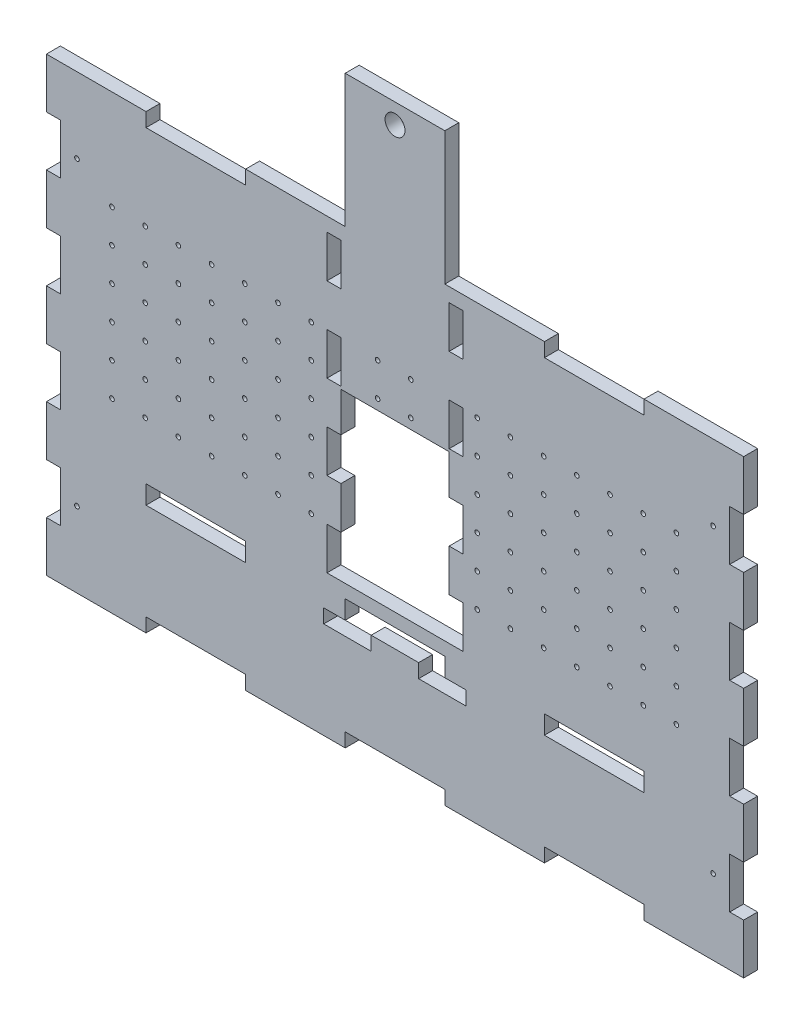
SolidWorks part; units mm, degrees
ref_plane "Front Plane" through (0, 0, 0) normal (0, 0, 1) x (1, 0, 0)
ref_plane "Top Plane" through (0, 0, 0) normal (0, 1, 0) x (1, 0, 0)
ref_plane "Right Plane" through (0, 0, 0) normal (1, 0, 0) x (0, 0, -1)
sketch "Sketch1" plane through (0, 0, 0) normal (0, 0, 1) x (1, 0, 0)
  line L1 (-127.8759, 88.4641) -> (138.8241, 88.4641)
  line L2 (-127.8759, 88.4641) -> (-127.8759, -84.2559)
  line L3 (-127.8759, -84.2559) -> (138.8241, -84.2559)
  line L4 (138.8241, 88.4641) -> (138.8241, -84.2559)
  dimension "D1" = 266.7
  dimension "D2" = 172.72
extrude "Boss-Extrude1" add sketch "Sketch1" along normal blind 5.334
sketch "Sketch2" plane through (0, 0, 5.334) normal (0, 0, 1) x (1, 0, 0)
  line L0 (-127.8759, -84.2559) -> (138.8241, -84.2559) construction
  line L1 (-89.7759, -84.2559) -> (-51.6759, -84.2559)
  line L2 (-89.7759, -84.2559) -> (-89.7759, -78.9219)
  line L3 (-89.7759, -78.9219) -> (-51.6759, -78.9219)
  line L4 (-51.6759, -84.2559) -> (-51.6759, -78.9219)
  line L5 (-89.7759, -78.9219) -> (-127.8759, -78.9219) construction
  line L6 (-13.5759, -84.2559) -> (24.5241, -84.2559)
  line L7 (-13.5759, -84.2559) -> (-13.5759, -78.9219)
  line L8 (-13.5759, -78.9219) -> (24.5241, -78.9219)
  line L9 (24.5241, -84.2559) -> (24.5241, -78.9219)
  line L10 (62.6241, -84.2559) -> (100.7241, -84.2559)
  line L11 (62.6241, -84.2559) -> (62.6241, -78.9219)
  line L12 (62.6241, -78.9219) -> (100.7241, -78.9219)
  line L13 (100.7241, -84.2559) -> (100.7241, -78.9219)
  line L14 (-127.8759, 88.4641) -> (-127.8759, -84.2559) construction
  line L15 (-51.6759, -78.9219) -> (-13.5759, -78.9219) construction
  line L16 (24.5241, -78.9219) -> (62.6241, -78.9219) construction
  line L17 (62.6241, -78.9219) -> (62.364, -79.7896) construction
  line L18 (100.7241, -78.9219) -> (138.8241, -78.9219) construction
  line L19 (138.8241, -84.2559) -> (138.8241, 88.4641) construction
  line L20 (-127.8759, 2.1041) -> (138.8241, 2.1041) construction
  line L21 (100.7241, 88.4641) -> (100.7241, 83.1301)
  line L22 (62.6241, 83.1301) -> (100.7241, 83.1301)
  line L23 (62.6241, 88.4641) -> (62.6241, 83.1301)
  line L24 (24.5241, 88.4641) -> (24.5241, 83.1301)
  line L25 (-13.5759, 83.1301) -> (24.5241, 83.1301)
  line L26 (-13.5759, 88.4641) -> (-13.5759, 83.1301)
  line L27 (-51.6759, 88.4641) -> (-51.6759, 83.1301)
  line L28 (-89.7759, 83.1301) -> (-51.6759, 83.1301)
  line L29 (-89.7759, 88.4641) -> (-89.7759, 83.1301)
  line L30 (62.6241, 88.4641) -> (100.7241, 88.4641)
  line L31 (-13.5759, 88.4641) -> (24.5241, 88.4641)
  line L32 (-89.7759, 88.4641) -> (-51.6759, 88.4641)
  dimension "D1" = 5.334
extrude "Cut-Extrude1" cut sketch "Sketch2" against normal through all
sketch "Sketch5" plane through (0, 0, 5.334) normal (0, 0, 1) x (1, 0, 0)
  line L0 (-51.6759, -34.8224) -> (-13.5759, -34.8224) construction
  line L1 (-89.7759, -34.8224) -> (-51.6759, -34.8224)
  line L2 (-89.7759, -34.8224) -> (-89.7759, -41.9344)
  line L3 (-89.7759, -41.9344) -> (-51.6759, -41.9344)
  line L4 (-51.6759, -34.8224) -> (-51.6759, -41.9344)
  line L5 (-13.5759, -34.8224) -> (24.5241, -34.8224)
  line L6 (-13.5759, -34.8224) -> (-13.5759, -41.9344)
  line L7 (-13.5759, -41.9344) -> (24.5241, -41.9344)
  line L8 (24.5241, -34.8224) -> (24.5241, -41.9344)
  line L9 (62.6241, -34.8224) -> (100.7241, -34.8224)
  line L10 (62.6241, -34.8224) -> (62.6241, -41.9344)
  line L11 (62.6241, -41.9344) -> (100.7241, -41.9344)
  line L12 (100.7241, -34.8224) -> (100.7241, -41.9344)
  line L13 (-51.6759, -41.9344) -> (-13.5759, -41.9344) construction
  line L14 (24.5241, -34.8224) -> (62.6241, -34.8224) construction
  line L15 (24.5241, -41.9344) -> (62.6241, -41.9344) construction
  line L16 (-89.7759, -34.8224) -> (-127.8759, -34.8224) construction
  line L17 (-127.8759, 88.4641) -> (-127.8759, -84.2559) construction
  line L18 (-89.7759, -41.9344) -> (-127.8759, -41.9344) construction
  line L19 (100.7241, -34.8224) -> (138.8241, -34.8224) construction
  line L20 (138.8241, -84.2559) -> (138.8241, 88.4641) construction
  line L21 (100.7241, -41.9344) -> (138.8241, -41.9344) construction
  dimension "D1" = 7.112
extrude "Cut-Extrude3" cut sketch "Sketch5" against normal through all
sketch "Sketch8" plane through (0, 0, 5.334) normal (0, 0, 1) x (1, 0, 0)
  line L0 (-13.5759, -41.9344) -> (24.5241, -41.9344) construction
  line L1 (-21.7977, -47.2684) -> (-3.6478, -47.2684)
  line L2 (-21.7977, -47.2684) -> (-21.7977, -41.9344)
  line L3 (-21.7977, -41.9344) -> (-3.6478, -41.9344)
  line L4 (-3.6478, -47.2684) -> (-3.6478, -41.9344)
  line L5 (-3.6478, -47.2684) -> (14.5022, -47.2684) construction
  line L6 (14.5022, -41.9344) -> (32.6521, -41.9344)
  line L7 (14.5022, -41.9344) -> (14.5022, -47.2684)
  line L8 (14.5022, -47.2684) -> (32.6521, -47.2684)
  line L9 (32.6521, -41.9344) -> (32.6521, -47.2684)
  line L10 (14.5022, -47.2684) -> (14.3218, -49.4005) construction
  line L11 (14.5022, -41.9344) -> (-3.6478, -41.9344) construction
  line L12 (62.6241, -34.8224) -> (62.6241, -41.9344) construction
  line L13 (-51.6759, -41.9344) -> (-51.6759, -34.8224) construction
  dimension "D1" = 5.334
  dimension "D2" = 29.972
  dimension "D3" = 29.8782
extrude "Cut-Extrude6" cut sketch "Sketch8" against normal through all
sketch "Sketch9" plane through (0, 0, 5.334) normal (0, 0, 1) x (1, 0, 0)
  line L0 (-127.8759, 88.4641) -> (-127.8759, -84.2559) construction
  line L1 (-127.8759, -65.0647) -> (-122.5419, -65.0647)
  line L2 (-127.8759, -65.0647) -> (-127.8759, -45.8736)
  line L3 (-127.8759, -45.8736) -> (-122.5419, -45.8736)
  line L4 (-122.5419, -65.0647) -> (-122.5419, -45.8736)
  line L5 (-122.5419, 69.273) -> (-122.5419, 88.4641) construction
  line L6 (-127.8759, -26.6825) -> (-122.5419, -26.6825)
  line L7 (-127.8759, -26.6825) -> (-127.8759, -7.4914)
  line L8 (-127.8759, -7.4914) -> (-122.5419, -7.4914)
  line L9 (-122.5419, -26.6825) -> (-122.5419, -7.4914)
  line L10 (-127.8759, 11.6997) -> (-122.5419, 11.6997)
  line L11 (-127.8759, 11.6997) -> (-127.8759, 30.8908)
  line L12 (-127.8759, 30.8908) -> (-122.5419, 30.8908)
  line L13 (-122.5419, 11.6997) -> (-122.5419, 30.8908)
  line L14 (-127.8759, 50.0819) -> (-122.5419, 50.0819)
  line L15 (-127.8759, 50.0819) -> (-127.8759, 69.273)
  line L16 (-127.8759, 69.273) -> (-122.5419, 69.273)
  line L17 (-122.5419, 50.0819) -> (-122.5419, 69.273)
  line L18 (-89.7759, 88.4641) -> (-127.8759, 88.4641) construction
  line L19 (-122.5419, 50.0819) -> (-122.5419, 30.8908) construction
  line L20 (-122.5419, 11.6997) -> (-122.5419, -7.4914) construction
  line L21 (-122.5419, -26.6825) -> (-122.5419, -45.8736) construction
  line L22 (-122.5419, -65.0647) -> (-122.5419, -84.2559) construction
  line L23 (-127.8759, -84.2559) -> (-89.7759, -84.2559) construction
  line L24 (5.4741, 83.1301) -> (5.4741, -78.9219) construction
  line L25 (-13.5759, 83.1301) -> (24.5241, 83.1301) construction
  line L26 (24.5241, -78.9219) -> (-13.5759, -78.9219) construction
  line L27 (133.4901, -65.0647) -> (133.4901, -84.2559) construction
  line L28 (133.4901, -26.6825) -> (133.4901, -45.8736) construction
  line L29 (133.4901, 11.6997) -> (133.4901, -7.4914) construction
  line L30 (133.4901, 50.0819) -> (133.4901, 30.8908) construction
  line L31 (133.4901, 69.273) -> (133.4901, 88.4641) construction
  line L32 (133.4901, 50.0819) -> (133.4901, 69.273)
  line L33 (138.8241, 69.273) -> (133.4901, 69.273)
  line L34 (138.8241, 50.0819) -> (138.8241, 69.273)
  line L35 (138.8241, 50.0819) -> (133.4901, 50.0819)
  line L36 (133.4901, 11.6997) -> (133.4901, 30.8908)
  line L37 (138.8241, 30.8908) -> (133.4901, 30.8908)
  line L38 (138.8241, 11.6997) -> (138.8241, 30.8908)
  line L39 (138.8241, 11.6997) -> (133.4901, 11.6997)
  line L40 (133.4901, -26.6825) -> (133.4901, -7.4914)
  line L41 (138.8241, -7.4914) -> (133.4901, -7.4914)
  line L42 (138.8241, -26.6825) -> (138.8241, -7.4914)
  line L43 (138.8241, -26.6825) -> (133.4901, -26.6825)
  line L44 (133.4901, -65.0647) -> (133.4901, -45.8736)
  line L45 (138.8241, -45.8736) -> (133.4901, -45.8736)
  line L46 (138.8241, -65.0647) -> (138.8241, -45.8736)
  line L47 (138.8241, -65.0647) -> (133.4901, -65.0647)
  dimension "D1" = 5.334
extrude "Cut-Extrude7" cut sketch "Sketch9" against normal through all
sketch "Sketch10" plane through (0, 88.4641, 0) normal (0, 1, 0) x (1, 0, 0)
  line L1 (24.5241, -5.334) -> (62.6241, -5.334)
  line L2 (24.5241, -5.334) -> (24.5241, 0)
  line L3 (24.5241, 0) -> (62.6241, 0)
  line L4 (62.6241, -5.334) -> (62.6241, 0)
extrude "Boss-Extrude2" add sketch "Sketch10" along normal blind 50.8
sketch "Sketch11" plane through (0, 0, 0) normal (0, 0, -1) x (-1, 0, 0)
  line L0 (-24.5241, 83.1301) -> (-24.5241, 139.2641) construction
  line L1 (-24.5241, 88.4641) -> (-31.1281, 88.4641)
  line L2 (-24.5241, 88.4641) -> (-24.5241, 129.1041)
  line L3 (-24.5241, 129.1041) -> (-31.1281, 129.1041)
  line L4 (-31.1281, 88.4641) -> (-31.1281, 129.1041)
  line L5 (13.5759, 88.4641) -> (51.6759, 88.4641) construction
  dimension "D1" = 6.604
  dimension "D2" = 40.64
  dimension "D3" = 0
extrude "Cut-Extrude8" cut sketch "Sketch11" against normal through all
sketch "Sketch12" plane through (0, 0, 5.334) normal (0, 0, 1) x (1, 0, 0)
  line L0 (62.6241, 139.2641) -> (62.6241, 83.1301) construction
  circle A0 centre (43.5741, 130.4765) radius 3.81
  dimension "D1" = 19.05
extrude "Cut-Extrude9" cut sketch "Sketch12" against normal through all
sketch "Sketch14" plane through (0, 0, 5.334) normal (0, 0, 1) x (1, 0, 0)
  line L0 (-89.7759, 88.4641) -> (-127.8759, 88.4641) construction
  circle A0 centre (-102.7976, 50.3641) radius 0.889
  circle A1 centre (-90.0976, 50.3641) radius 0.889
  circle A2 centre (-77.3976, 50.3641) radius 0.889
  circle A3 centre (-64.6976, 50.3641) radius 0.889
  circle A4 centre (-51.9976, 50.3641) radius 0.889
  circle A5 centre (-39.2976, 50.3641) radius 0.889
  circle A6 centre (-26.5976, 50.3641) radius 0.889
  circle A8 centre (-1.1976, 50.3641) radius 0.889
  circle A9 centre (11.5024, 50.3641) radius 0.889
  circle A11 centre (36.9024, 50.3641) radius 0.889
  circle A12 centre (49.6024, 50.3641) radius 0.889
  circle A13 centre (62.3024, 50.3641) radius 0.889
  circle A14 centre (75.0024, 50.3641) radius 0.889
  circle A15 centre (87.7024, 50.3641) radius 0.889
  circle A16 centre (100.4024, 50.3641) radius 0.889
  circle A17 centre (113.1024, 50.3641) radius 0.889
  circle A18 centre (-102.7976, 37.6641) radius 0.889
  circle A19 centre (-90.0976, 37.6641) radius 0.889
  circle A20 centre (-77.3976, 37.6641) radius 0.889
  circle A21 centre (-64.6976, 37.6641) radius 0.889
  circle A22 centre (-51.9976, 37.6641) radius 0.889
  circle A23 centre (-39.2976, 37.6641) radius 0.889
  circle A24 centre (-26.5976, 37.6641) radius 0.889
  circle A26 centre (-1.1976, 37.6641) radius 0.889
  circle A27 centre (11.5024, 37.6641) radius 0.889
  circle A29 centre (36.9024, 37.6641) radius 0.889
  circle A30 centre (49.6024, 37.6641) radius 0.889
  circle A31 centre (62.3024, 37.6641) radius 0.889
  circle A32 centre (75.0024, 37.6641) radius 0.889
  circle A33 centre (87.7024, 37.6641) radius 0.889
  circle A34 centre (100.4024, 37.6641) radius 0.889
  circle A35 centre (113.1024, 37.6641) radius 0.889
  circle A36 centre (-102.7976, 24.9641) radius 0.889
  circle A37 centre (-90.0976, 24.9641) radius 0.889
  circle A38 centre (-77.3976, 24.9641) radius 0.889
  circle A39 centre (-64.6976, 24.9641) radius 0.889
  circle A40 centre (-51.9976, 24.9641) radius 0.889
  circle A41 centre (-39.2976, 24.9641) radius 0.889
  circle A42 centre (-26.5976, 24.9641) radius 0.889
  circle A44 centre (-1.1976, 24.9641) radius 0.889
  circle A45 centre (11.5024, 24.9641) radius 0.889
  circle A47 centre (36.9024, 24.9641) radius 0.889
  circle A48 centre (49.6024, 24.9641) radius 0.889
  circle A49 centre (62.3024, 24.9641) radius 0.889
  circle A50 centre (75.0024, 24.9641) radius 0.889
  circle A51 centre (87.7024, 24.9641) radius 0.889
  circle A52 centre (100.4024, 24.9641) radius 0.889
  circle A53 centre (113.1024, 24.9641) radius 0.889
  circle A54 centre (-102.7976, 12.2641) radius 0.889
  circle A55 centre (-90.0976, 12.2641) radius 0.889
  circle A56 centre (-77.3976, 12.2641) radius 0.889
  circle A57 centre (-64.6976, 12.2641) radius 0.889
  circle A58 centre (-51.9976, 12.2641) radius 0.889
  circle A59 centre (-39.2976, 12.2641) radius 0.889
  circle A60 centre (-26.5976, 12.2641) radius 0.889
  circle A65 centre (36.9024, 12.2641) radius 0.889
  circle A66 centre (49.6024, 12.2641) radius 0.889
  circle A67 centre (62.3024, 12.2641) radius 0.889
  circle A68 centre (75.0024, 12.2641) radius 0.889
  circle A69 centre (87.7024, 12.2641) radius 0.889
  circle A70 centre (100.4024, 12.2641) radius 0.889
  circle A71 centre (113.1024, 12.2641) radius 0.889
  circle A72 centre (-102.7976, -0.4359) radius 0.889
  circle A73 centre (-90.0976, -0.4359) radius 0.889
  circle A74 centre (-77.3976, -0.4359) radius 0.889
  circle A75 centre (-64.6976, -0.4359) radius 0.889
  circle A76 centre (-51.9976, -0.4359) radius 0.889
  circle A77 centre (-39.2976, -0.4359) radius 0.889
  circle A78 centre (-26.5976, -0.4359) radius 0.889
  circle A79 centre (-13.8976, -0.4359) radius 0.889
  circle A80 centre (-1.1976, -0.4359) radius 0.889
  circle A81 centre (11.5024, -0.4359) radius 0.889
  circle A82 centre (24.2024, -0.4359) radius 0.889
  circle A83 centre (36.9024, -0.4359) radius 0.889
  circle A84 centre (49.6024, -0.4359) radius 0.889
  circle A85 centre (62.3024, -0.4359) radius 0.889
  circle A86 centre (75.0024, -0.4359) radius 0.889
  circle A87 centre (87.7024, -0.4359) radius 0.889
  circle A88 centre (100.4024, -0.4359) radius 0.889
  circle A89 centre (113.1024, -0.4359) radius 0.889
  circle A90 centre (-102.7976, -13.1359) radius 0.889
  circle A91 centre (-90.0976, -13.1359) radius 0.889
  circle A92 centre (-77.3976, -13.1359) radius 0.889
  circle A93 centre (-64.6976, -13.1359) radius 0.889
  circle A94 centre (-51.9976, -13.1359) radius 0.889
  circle A95 centre (-39.2976, -13.1359) radius 0.889
  circle A96 centre (-26.5976, -13.1359) radius 0.889
  circle A97 centre (-13.8976, -13.1359) radius 0.889
  circle A98 centre (-1.1976, -13.1359) radius 0.889
  circle A99 centre (11.5024, -13.1359) radius 0.889
  circle A100 centre (24.2024, -13.1359) radius 0.889
  circle A101 centre (36.9024, -13.1359) radius 0.889
  circle A102 centre (49.6024, -13.1359) radius 0.889
  circle A103 centre (62.3024, -13.1359) radius 0.889
  circle A104 centre (75.0024, -13.1359) radius 0.889
  circle A105 centre (87.7024, -13.1359) radius 0.889
  circle A106 centre (100.4024, -13.1359) radius 0.889
  circle A107 centre (113.1024, -13.1359) radius 0.889
  circle A108 centre (-1.1976, 12.2641) radius 0.889 [skipped]
  circle A110 centre (11.5024, 12.2641) radius 0.889 [skipped]
  circle A116 centre (24.2024, 50.3641) radius 0.889 [skipped]
  circle A117 centre (-13.8976, 50.3641) radius 0.889 [skipped]
  dimension "D1" = 18
  dimension "D2" = 38.1
  dimension "D4" = 1.778
  dimension "D3" = 6
extrude "Cut-Extrude11" cut sketch "Sketch14" against normal through all
sketch "Sketch15" plane through (0, 0, 5.334) normal (0, 0, 1) x (1, 0, 0)
  line L1 (31.1281, 129.1041) -> (24.5241, 129.1041)
  line L2 (31.1281, 129.1041) -> (31.1281, 139.2641)
  line L3 (31.1281, 139.2641) -> (24.5241, 139.2641)
  line L4 (24.5241, 129.1041) -> (24.5241, 139.2641)
extrude "Cut-Extrude12" cut sketch "Sketch15" against normal through all
sketch "Sketch16" plane through (0, 0, 5.334) normal (0, 0, 1) x (1, 0, 0)
  line L0 (5.4741, 83.1301) -> (5.4741, -78.9219) construction
  line L1 (-15.2269, 33.7576) -> (26.1751, 33.7576)
  line L2 (-15.2269, 33.7576) -> (-15.2269, -29.7424)
  line L3 (-15.2269, -29.7424) -> (26.1751, -29.7424)
  line L4 (26.1751, 33.7576) -> (26.1751, -29.7424)
  line L5 (-13.5759, 83.1301) -> (24.5241, 83.1301) construction
  line L6 (24.5241, -78.9219) -> (-13.5759, -78.9219) construction
  line L7 (24.5241, -34.8224) -> (-13.5759, -34.8224) construction
  dimension "D1" = 63.5
  dimension "D2" = 41.402
  dimension "D3" = 20.701
  dimension "D4" = 5.08
extrude "Cut-Extrude13" cut sketch "Sketch16" against normal through all
sketch "Sketch17" plane through (0, 0, 5.334) normal (0, 0, 1) x (1, 0, 0)
  line L0 (-15.2269, 33.7576) -> (-15.2269, -29.7424) construction
  line L1 (-15.2269, -29.7424) -> (-20.5609, -29.7424)
  line L2 (-15.2269, -29.7424) -> (-15.2269, -13.6178)
  line L3 (-15.2269, -13.6178) -> (-20.5609, -13.6178)
  line L4 (-20.5609, -29.7424) -> (-20.5609, -13.6178)
  line L5 (-15.2269, 2.5069) -> (-20.5609, 2.5069)
  line L6 (-15.2269, 2.5069) -> (-15.2269, 18.6315)
  line L7 (-15.2269, 18.6315) -> (-20.5609, 18.6315)
  line L8 (-20.5609, 2.5069) -> (-20.5609, 18.6315)
  line L9 (-20.5609, -13.6178) -> (-20.5609, 2.5069) construction
  line L10 (-20.5609, 50.8808) -> (-15.2269, 50.8808)
  line L11 (-20.5609, 50.8808) -> (-20.5609, 34.7562)
  line L12 (-20.5609, 34.7562) -> (-15.2269, 34.7562)
  line L13 (-15.2269, 50.8808) -> (-15.2269, 34.7562)
  line L14 (-20.5609, 67.0055) -> (-15.2269, 67.0055)
  line L15 (-20.5609, 67.0055) -> (-20.5609, 83.1301)
  line L16 (-20.5609, 83.1301) -> (-15.2269, 83.1301)
  line L17 (-15.2269, 67.0055) -> (-15.2269, 83.1301)
  line L18 (-20.5609, 18.6315) -> (-20.5609, 34.7562) construction
  line L19 (-20.5609, 67.0055) -> (-20.5609, 50.8808) construction
  line L20 (5.4741, 83.1301) -> (5.4741, -78.9219) construction
  line L21 (-13.5759, 83.1301) -> (24.5241, 83.1301) construction
  line L22 (24.5241, -78.9219) -> (-13.5759, -78.9219) construction
  line L23 (31.5091, 67.0055) -> (31.5091, 50.8808) construction
  line L24 (31.5091, 18.6315) -> (31.5091, 34.7562) construction
  line L25 (31.5091, -13.6178) -> (31.5091, 2.5069) construction
  line L26 (26.1751, 67.0055) -> (26.1751, 83.1301)
  line L27 (31.5091, 83.1301) -> (26.1751, 83.1301)
  line L28 (31.5091, 67.0055) -> (31.5091, 83.1301)
  line L29 (31.5091, 67.0055) -> (26.1751, 67.0055)
  line L30 (26.1751, 50.8808) -> (26.1751, 34.7562)
  line L31 (31.5091, 34.7562) -> (26.1751, 34.7562)
  line L32 (31.5091, 50.8808) -> (31.5091, 34.7562)
  line L33 (31.5091, 50.8808) -> (26.1751, 50.8808)
  line L34 (31.5091, 2.5069) -> (31.5091, 18.6315)
  line L35 (26.1751, 18.6315) -> (31.5091, 18.6315)
  line L36 (26.1751, 2.5069) -> (26.1751, 18.6315)
  line L37 (26.1751, 2.5069) -> (31.5091, 2.5069)
  line L38 (31.5091, -29.7424) -> (31.5091, -13.6178)
  line L39 (26.1751, -13.6178) -> (31.5091, -13.6178)
  line L40 (26.1751, -29.7424) -> (26.1751, -13.6178)
  line L41 (26.1751, -29.7424) -> (31.5091, -29.7424)
  dimension "D1" = 0
  dimension "D2" = 5.334
  dimension "D3" = 5.334
  dimension "D4" = 5.334
extrude "Cut-Extrude14" cut sketch "Sketch17" against normal through all
sketch "Sketch18" plane through (0, 0, 5.334) normal (0, 0, 1) x (1, 0, 0)
  line L0 (24.5241, 83.1301) -> (24.5241, 148.9274) construction
  line L1 (31.1281, 139.2641) -> (62.6241, 139.2641) construction
  line L2 (-13.5759, 83.1301) -> (24.5241, 83.1301)
  line L3 (-13.5759, 83.1301) -> (-13.5759, 139.2641)
  line L4 (-13.5759, 139.2641) -> (24.5241, 139.2641)
  line L5 (24.5241, 83.1301) -> (24.5241, 139.2641)
  dimension "D1" = 0
extrude "Boss-Extrude3" add sketch "Sketch18" against normal blind 5.334
sketch "Sketch19" plane through (0, 0, 5.334) normal (0, 0, 1) x (1, 0, 0)
  line L1 (31.1281, 88.4641) -> (65.8849, 88.4641)
  line L2 (31.1281, 88.4641) -> (31.1281, 143.4078)
  line L3 (31.1281, 143.4078) -> (65.8849, 143.4078)
  line L4 (65.8849, 88.4641) -> (65.8849, 143.4078)
extrude "Cut-Extrude15" cut sketch "Sketch19" against normal through all
sketch "Sketch20" plane through (0, 0, 5.334) normal (0, 0, 1) x (1, 0, 0)
  line L0 (5.4741, 139.2641) -> (5.4741, 29.9476) construction
  line L1 (24.5241, 139.2641) -> (-13.5759, 139.2641) construction
  circle A0 centre (5.4741, 131.6441) radius 3.81
  point P8 (-119.488, 123.581)
  dimension "D1" = 7.62
  dimension "D3" = 7.62
  dimension "D2" = 0
extrude "Cut-Extrude16" cut sketch "Sketch20" against normal through all contours A0
sketch "Sketch21" plane through (0, 0, 5.334) normal (0, 0, 1) x (1, 0, 0)
  line L0 (133.4901, 59.6775) -> (-122.5419, 59.6775) construction
  line L1 (133.4901, 69.273) -> (133.4901, 50.0819) construction
  line L2 (-122.5419, 50.0819) -> (-122.5419, 69.273) construction
  line L3 (-122.5419, -55.4692) -> (133.4901, -55.4692) construction
  line L4 (-122.5419, -65.0647) -> (-122.5419, -45.8736) construction
  line L5 (133.4901, -45.8736) -> (133.4901, -65.0647) construction
  line L6 (138.8241, 2.1041) -> (-127.8759, 2.1041) construction
  line L7 (138.8241, -7.4914) -> (138.8241, 11.6997) construction
  line L8 (-127.8759, 11.6997) -> (-127.8759, -7.4914) construction
  line L9 (5.4741, 139.2641) -> (5.4741, -78.9219) construction
  line L10 (24.5241, 139.2641) -> (-13.5759, 139.2641) construction
  line L11 (24.5241, -78.9219) -> (-13.5759, -78.9219) construction
  circle A0 centre (127.1401, 59.6775) radius 0.889
  circle A1 centre (-116.1919, 59.6775) radius 0.889
  circle A2 centre (-116.1919, -55.4692) radius 0.889
  circle A3 centre (127.1401, -55.4692) radius 0.889
  dimension "D1" = 1.778
  dimension "D2" = 0
  dimension "D3" = 6.35
extrude "Cut-Extrude17" cut sketch "Sketch21" against normal through all
equation "\"MDF\"= .21in"
equation "\"Foamcore\"= .13in"
equation "\"Gmaterial\"= \"MDF\""
equation "\"D1@Boss-Extrude1\"=\"MDF\""
equation "\"D1@Sketch2\"=\"MDF\""
equation "\"D1@Sketch5\"=\"MDF\"+0.07"
equation "\"D1@Sketch8\"=\"MDF\""
equation "\"D1@Sketch9\"=\"MDF\""
equation "\"D1@Sketch11\"=\"MDF\"+.05"
equation "\"D2@Sketch17\"=\"MDF\""
equation "\"D3@Sketch17\"=\"MDF\""
equation "\"D4@Sketch17\"=\"MDF\""
equation "\"D1@Boss-Extrude3\"=\"MDF\""
